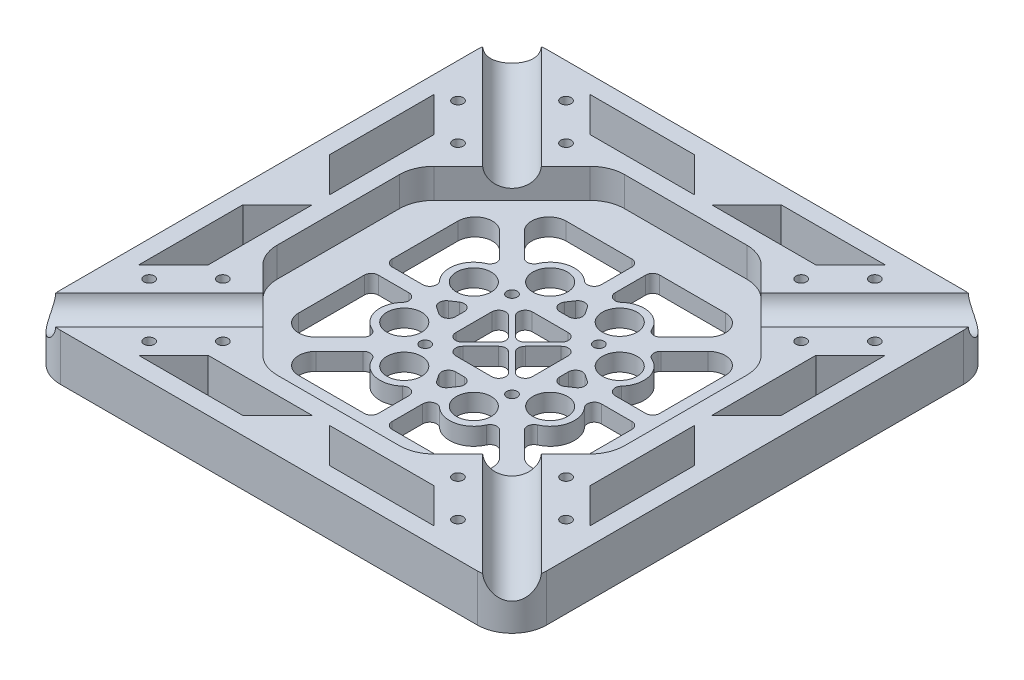
SolidWorks part; units mm, degrees
ref_plane "Plan de face" through (0, 0, 0) normal (0, 0, 1) x (1, 0, 0)
ref_plane "Plan de dessus" through (0, 0, 0) normal (0, 1, 0) x (1, 0, 0)
ref_plane "Plan de droite" through (0, 0, 0) normal (1, 0, 0) x (0, 0, -1)
sketch "Esquisse1" plane through (0, 0, 0) normal (0, 1, 0) x (1, 0, 0)
  line L0 (55, 75.9996) -> (55, -81.4607) construction
  line L1 (-70, 70) -> (70, 70)
  line L2 (-70, 70) -> (-70, -70)
  line L3 (-70, -70) -> (70, -70)
  line L4 (70, 70) -> (70, -70)
  line L5 (0, 0) -> (40, -40) construction
  line L6 (-12.5, 12.5) -> (12.5, 12.5) construction
  line L7 (0, 0) -> (-40, -40) construction
  line L8 (-15, 5) -> (-15, -5)
  line L9 (65, 75.9996) -> (65, -81.4607) construction
  line L10 (50, 0) -> (70, 0) construction
  line L11 (52.5, 0) -> (65, 12.5) construction
  line L12 (65, 12.5) -> (55, 2.5)
  line L13 (65, -12.5) -> (52.5, 0) construction
  line L14 (65, -12.5) -> (55, -2.5)
  line L15 (65, -12.5) -> (65, -42.5)
  line L16 (65, -42.5) -> (55, -32.5)
  line L17 (55, -32.5) -> (55, -2.5)
  line L18 (65, 12.5) -> (65, 42.5)
  line L19 (65, 42.5) -> (55, 32.5)
  line L20 (55, 32.5) -> (55, 2.5)
  line L21 (12.5, -65) -> (2.5, -55)
  line L22 (-12.5, -65) -> (-2.5, -55)
  line L23 (-12.5, -65) -> (-42.5, -65)
  line L24 (-42.5, -65) -> (-32.5, -55)
  line L25 (-32.5, -55) -> (-2.5, -55)
  line L26 (12.5, -65) -> (42.5, -65)
  line L27 (42.5, -65) -> (32.5, -55)
  line L28 (32.5, -55) -> (2.5, -55)
  line L29 (0, -52.5) -> (12.5, -65) construction
  line L30 (-12.5, -65) -> (0, -52.5) construction
  line L31 (-65, -12.5) -> (-55, -2.5)
  line L32 (-65, 12.5) -> (-55, 2.5)
  line L33 (-65, 12.5) -> (-65, 42.5)
  line L34 (-65, 42.5) -> (-55, 32.5)
  line L35 (-55, 32.5) -> (-55, 2.5)
  line L36 (-65, -12.5) -> (-65, -42.5)
  line L37 (-65, -42.5) -> (-55, -32.5)
  line L38 (-55, -32.5) -> (-55, -2.5)
  line L39 (-52.5, 0) -> (-65, -12.5) construction
  line L40 (-65, 12.5) -> (-52.5, 0) construction
  line L41 (-12.5, 65) -> (-2.5, 55)
  line L42 (12.5, 65) -> (2.5, 55)
  line L43 (12.5, 65) -> (42.5, 65)
  line L44 (42.5, 65) -> (32.5, 55)
  line L45 (32.5, 55) -> (2.5, 55)
  line L46 (-12.5, 65) -> (-42.5, 65)
  line L47 (-42.5, 65) -> (-32.5, 55)
  line L48 (-32.5, 55) -> (-2.5, 55)
  line L49 (0, 52.5) -> (-12.5, 65) construction
  line L50 (12.5, 65) -> (0, 52.5) construction
  line L51 (-40, -40) -> (40, -40) construction
  line L52 (40, -40) -> (40, 40) construction
  line L53 (40, 40) -> (-40, 40) construction
  line L54 (-40, 40) -> (-40, -40) construction
  line L55 (-5, -15) -> (5, -15)
  line L56 (5, -15) -> (0, -22.5)
  line L57 (0, -22.5) -> (-5, -15)
  line L58 (0, -22.5) -> (0, -40) construction
  line L59 (0, -1) -> (-10, -11)
  line L60 (-10, -11) -> (10, -11)
  line L61 (10, -11) -> (0, -1)
  line L62 (-34.9645, -38.5) -> (-14.0078, -17.5434) construction
  line L63 (-34.9645, -38.5) -> (-2, -38.5)
  line L64 (-2, -38.5) -> (-2, -21)
  line L65 (2, -38.5) -> (2, -21)
  line L66 (34.9645, -38.5) -> (2, -38.5)
  line L67 (34.9645, -38.5) -> (13.7697, -17.3052) construction
  line L68 (-16.9983, -20.5339) -> (-34.9645, -38.5)
  line L69 (-15, -5) -> (-22.5, 0)
  line L70 (-22.5, 0) -> (-15, 5)
  line L71 (-1, 0) -> (-11, 10)
  line L72 (-11, 10) -> (-11, -10)
  line L73 (-11, -10) -> (-1, 0)
  line L74 (-38.5, 34.9645) -> (-38.5, 2)
  line L75 (-38.5, 2) -> (-21, 2)
  line L76 (-38.5, -2) -> (-21, -2)
  line L77 (-38.5, -34.9645) -> (-38.5, -2)
  line L78 (-20.5339, 16.9983) -> (-38.5, 34.9645)
  line L79 (-20.5339, -16.9983) -> (-38.5, -34.9645)
  line L80 (-21, 2) -> (-24.408, 3.8995)
  line L81 (-12.5, 12.5) -> (-12.5, -12.5) construction
  line L82 (-21, -2) -> (-24.408, -3.8995)
  line L83 (-38.5, 34.9645) -> (-17.5434, 14.0078) construction
  line L84 (-38.5, -34.9645) -> (-17.3052, -13.7697) construction
  line L85 (-12.5, 12.5) -> (-12.5, -12.5) construction
  line L86 (5, 15) -> (-5, 15)
  line L87 (-5, 15) -> (0, 22.5)
  line L88 (0, 22.5) -> (5, 15)
  line L89 (0, 1) -> (10, 11)
  line L90 (10, 11) -> (-10, 11)
  line L91 (-10, 11) -> (0, 1)
  line L92 (34.9645, 38.5) -> (2, 38.5)
  line L93 (2, 38.5) -> (2, 21)
  line L94 (-2, 38.5) -> (-2, 21)
  line L95 (-34.9645, 38.5) -> (-2, 38.5)
  line L96 (-12.5, -12.5) -> (12.5, -12.5) construction
  line L97 (16.9983, 20.5339) -> (34.9645, 38.5)
  line L98 (-16.9983, 20.5339) -> (-34.9645, 38.5)
  line L99 (2, 21) -> (3.8995, 24.408)
  line L100 (-2, 21) -> (-3.8995, 24.408)
  line L101 (34.9645, 38.5) -> (14.0078, 17.5434) construction
  line L102 (-34.9645, 38.5) -> (-13.7697, 17.3052) construction
  line L103 (12.5, 12.5) -> (-12.5, 12.5) construction
  line L104 (15, -5) -> (15, 5)
  line L105 (15, 5) -> (22.5, 0)
  line L106 (22.5, 0) -> (15, -5)
  line L107 (1, 0) -> (11, -10)
  line L108 (11, -10) -> (11, 10)
  line L109 (11, 10) -> (1, 0)
  line L110 (38.5, -34.9645) -> (38.5, -2)
  line L111 (12.5, 12.5) -> (12.5, -12.5) construction
  line L112 (38.5, -2) -> (21, -2)
  line L113 (38.5, 2) -> (21, 2)
  line L114 (38.5, 34.9645) -> (38.5, 2)
  line L115 (20.5339, -16.9983) -> (38.5, -34.9645)
  line L116 (20.5339, 16.9983) -> (38.5, 34.9645)
  line L117 (21, -2) -> (24.408, -3.8995)
  line L118 (16.9983, -20.5339) -> (34.9645, -38.5)
  line L119 (-2, -21) -> (-3.8995, -24.408)
  line L120 (2, -21) -> (3.8995, -24.408)
  line L121 (21, 2) -> (24.408, 3.8995)
  line L122 (38.5, -34.9645) -> (17.5434, -14.0078) construction
  line L123 (38.5, 34.9645) -> (17.3052, 13.7697) construction
  line L124 (12.5, -12.5) -> (12.5, 12.5) construction
  circle A0 centre (-10.0139, -21) radius 5
  circle A1 centre (10.0139, -21) radius 5
  arc A2 (-3.8995, -24.408) -> (-16.9983, -20.5339) centre (-10.0139, -21) cw
  arc A3 (3.8995, -24.408) -> (16.9983, -20.5339) centre (10.0139, -21) ccw
  circle A4 centre (-21, 10.0139) radius 5
  circle A5 centre (-21, -10.0139) radius 5
  arc A6 (-24.408, 3.8995) -> (-20.5339, 16.9983) centre (-21, 10.0139) cw
  arc A7 (-24.408, -3.8995) -> (-20.5339, -16.9983) centre (-21, -10.0139) ccw
  circle A8 centre (-12.5, 12.5) radius 1.5
  circle A9 centre (10.0139, 21) radius 5
  circle A10 centre (-10.0139, 21) radius 5
  arc A11 (3.8995, 24.408) -> (16.9983, 20.5339) centre (10.0139, 21) cw
  arc A12 (-3.8995, 24.408) -> (-16.9983, 20.5339) centre (-10.0139, 21) ccw
  circle A13 centre (12.5, 12.5) radius 1.5
  circle A14 centre (21, -10.0139) radius 5
  circle A15 centre (21, 10.0139) radius 5
  circle A16 centre (-12.5, -12.5) radius 1.5
  arc A17 (24.408, -3.8995) -> (20.5339, -16.9983) centre (21, -10.0139) cw
  arc A18 (24.408, 3.8995) -> (20.5339, 16.9983) centre (21, 10.0139) ccw
  circle A19 centre (12.5, -12.5) radius 1.5
  dimension "D18" = 10
  dimension "D19" = 10
  dimension "D29" = 7
  dimension "D30" = 7
  dimension "D49" = 3
  dimension "D50" = 4
  dimension "D1" = 140
  dimension "D2" = 140
  dimension "D3" = 70
  dimension "D4" = 70
  dimension "D5" = 25
  dimension "D6" = 2.5
  dimension "D7" = 1.5
  dimension "D8" = 1.5
  dimension "D9" = 7.5
  dimension "D10" = 5
  dimension "D11" = 2.5
  dimension "D12" = 12.5
  dimension "D13" = 30
  dimension "D14" = 30
  dimension "D15" = 30
  dimension "D16" = 30
  dimension "D20" = 7.5
  dimension "D21" = 7.5
  dimension "D22" = 10
  dimension "D23" = 5
  dimension "D24" = 2
  dimension "D25" = 2
  dimension "D26" = 1.5
  dimension "D27" = 17.5
  dimension "D28" = 17.5
  dimension "D31" = 80
  dimension "D32" = 40
  dimension "D33" = 20
  dimension "D34" = 15
  dimension "D35" = 70
  dimension "D36" = 80
  dimension "D37" = 40
  dimension "D38" = 25
  dimension "D39" = 12.5
  dimension "D40" = 12.5
  dimension "D41" = 20
  dimension "D42" = 10
  dimension "D43" = 10
  dimension "D44" = 2.5
  dimension "D45" = 8.5
  dimension "D46" = 2.5
  dimension "D47" = 2.5
  dimension "D48" = 8.5
  dimension "D17" = 4
extrude "Boss.-Extru.1" add sketch "Esquisse1" along normal blind 13.5
ref_plane "Plan1" through (0, 0, 0) normal (0.7071, 0, 0.7071) x (0.7071, 0, -0.7071)
sketch "Esquisse4" plane through (0, 13.5, 0) normal (0, 1, 0) x (1, 0, 0)
  line L0 (-70, 70) -> (-70, -70) construction
  line L1 (-50, 50) -> (50, 50) construction
  line L2 (-50, 50) -> (-50, -50) construction
  line L3 (-50, -50) -> (50, -50) construction
  line L4 (50, 50) -> (50, -50) construction
  line L5 (70, 70) -> (-70, 70) construction
  line L6 (-37.6256, -34.0901) -> (-34.0901, -37.6256) construction
  line L7 (37.6256, -34.0901) -> (34.0901, -37.6256) construction
  line L8 (-34.0901, 37.6256) -> (-37.6256, 34.0901) construction
  line L9 (34.0901, 37.6256) -> (37.6256, 34.0901) construction
  line L10 (-21.7157, -50) -> (21.7157, -50)
  line L11 (21.7157, -50) -> (50, -21.7157)
  line L12 (50, -21.7157) -> (50, 21.7157)
  line L13 (50, 21.7157) -> (21.7157, 50)
  line L14 (21.7157, 50) -> (-21.7157, 50)
  line L15 (-21.7157, 50) -> (-50, 21.7157)
  line L16 (-50, 21.7157) -> (-50, -21.7157)
  line L17 (-50, -21.7157) -> (-21.7157, -50)
  dimension "D1" = 100
  dimension "D2" = 100
  dimension "D3" = 20
  dimension "D4" = 20
  dimension "D5" = 20
  dimension "D6" = 20
  dimension "D7" = 20
  dimension "D8" = 20
extrude "Enlèv. mat.-Extru.3" cut sketch "Esquisse4" against normal blind 8.5
sketch "Esquisse2" plane through (0, 0, 0) normal (0.7071, 0, 0.7071) x (0.7071, 0, -0.7071)
  line L0 (99.7696, 14) -> (-97.6372, 14) construction
  line L1 (-6, 14) -> (6, 14)
  arc A0 (-6, 14) -> (6, 14) centre (0, 14) ccw
  dimension "D1" = 14
extrude "Enlèv. mat.-Extru.1" cut sketch "Esquisse2" against normal blind 100 and the other way blind 100
ref_axis "Axe1" through (0, -76.1877, 0) along (0, 1, 0)
pattern_circular "Répétition circulaire1" count 2 every 90 about axis through (0, -76.1877, 0) along (0, 1, 0) of "Enlèv. mat.-Extru.1"
fillet "Congé1" radius 10 12 edges at (-70, 4, -70) (-70, 4, 70) (70, 4, -70) (70, 4, 70) (21.7157, 9.25, -50) (50, 9.25, -21.7157) (50, 9.25, 21.7157) (21.7157, 9.25, 50) (-21.7157, 9.25, 50) (-50, 9.25, 21.7157) (-21.7157, 9.25, -50) (-50, 9.25, -21.7157)
sketch "Esquisse3" plane through (0, 13.5, 0) normal (0, 1, 0) x (-1, 0, 0)
  line L2 (33.5465, 33.5465) -> (-33.5465, -33.5465) construction
  line L3 (70, -60) -> (70, 60) construction
  line L4 (60, 70) -> (-60, 70) construction
  circle A0 centre (44.4437, 60) radius 1.5
  circle A1 centre (60, 44.4437) radius 1.5
  circle A2 centre (60, -44.4437) radius 1.5
  circle A3 centre (44.4437, -60) radius 1.5
  circle A4 centre (-44.4437, -60) radius 1.5
  circle A5 centre (-60, -44.4437) radius 1.5
  circle A6 centre (-60, 44.4437) radius 1.5
  circle A7 centre (-44.4437, 60) radius 1.5
  circle A8 centre (49.3934, 33.837) radius 1.5
  circle A9 centre (33.837, 49.3934) radius 1.5
  circle A10 centre (33.837, -49.3934) radius 1.5
  circle A11 centre (49.3934, -33.837) radius 1.5
  circle A12 centre (-49.3934, -33.837) radius 1.5
  circle A13 centre (-33.837, -49.3934) radius 1.5
  circle A14 centre (-33.837, 49.3934) radius 1.5
  circle A15 centre (-49.3934, 33.837) radius 1.5
  dimension "D1" = 3
  dimension "D2" = 3
  dimension "D8" = 3
  dimension "D9" = 3
  dimension "D3" = 10
  dimension "D4" = 10
  dimension "D5" = 11
  dimension "D6" = 11
  dimension "D10" = 11
  dimension "D11" = 11
  dimension "D12" = 15
  dimension "D13" = 15
  dimension "D7" = 4
  dimension "D14" = 4
extrude "Enlèv. mat.-Extru.2" cut sketch "Esquisse3" against normal blind 13.5
fillet "Congé2" radius 5 8 edges at (-34.9645, 4.2728, 38.5) (34.9645, 4.2728, 38.5) (-38.5, 4.2728, -34.9645) (-34.9645, 4.2728, -38.5) (34.9645, 4.2728, -38.5) (38.5, 4.2728, -34.9645) (38.5, 4.2728, 34.9645) (-38.5, 4.2728, 34.9645)
fillet "Congé3" radius 2 48 edges at (2, 2.5, 38.5) (-2, 2.5, 38.5) (16.9983, 2.5, 20.5339) (2, 2.5, 21) (-2, 2.5, 21) (-16.9983, 2.5, 20.5339) (0, 2.5, 22.5) (-5, 2.5, 15) (5, 2.5, 15) (10, 2.5, 11) (0, 2.5, 1) (-10, 2.5, 11) (-38.5, 2.5, -2) (-38.5, 2.5, 2) (2, 2.5, -38.5) (-2, 2.5, -38.5) (38.5, 2.5, -2) (38.5, 2.5, 2) (21, 2.5, 2) (20.5339, 2.5, 16.9983) (21, 2.5, -2) (20.5339, 2.5, -16.9983) (16.9983, 2.5, -20.5339) (2, 2.5, -21) (-2, 2.5, -21) (-16.9983, 2.5, -20.5339) (-20.5339, 2.5, -16.9983) (-21, 2.5, -2) (-20.5339, 2.5, 16.9983) (-21, 2.5, 2) (-15, 2.5, 5) (-15, 2.5, -5) (-22.5, 2.5, 0) (-11, 2.5, 10) (-11, 2.5, -10) (-1, 2.5, 0) (5, 2.5, -15) (-5, 2.5, -15) (0, 2.5, -22.5) (10, 2.5, -11) (-10, 2.5, -11) (0, 2.5, -1) (15, 2.5, 5) (15, 2.5, -5) (22.5, 2.5, 0) (11, 2.5, 10) (11, 2.5, -10) (1, 2.5, 0)
